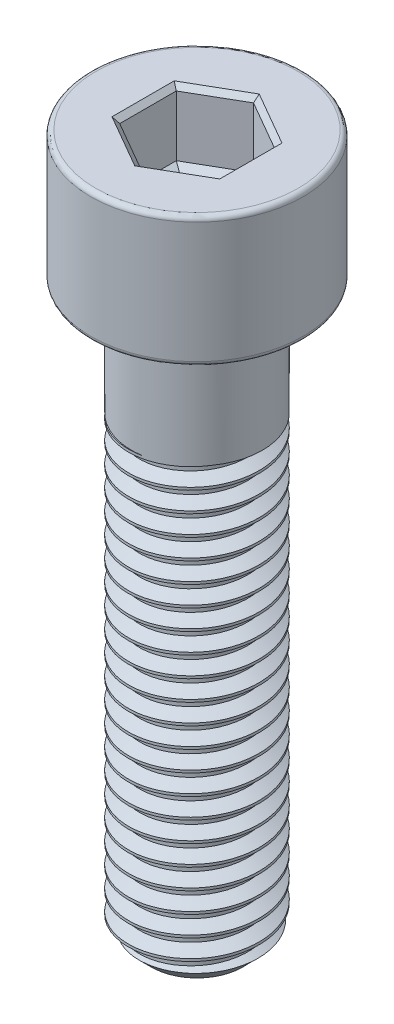
SolidWorks part; units mm, degrees
material "AISI Type A2 Tool Steel"
ref_plane "Front Plane" through (0, 0, 0) normal (0, 0, 1) x (1, 0, 0)
ref_plane "Top Plane" through (0, 0, 0) normal (0, 1, 0) x (1, 0, 0)
ref_plane "Right Plane" through (0, 0, 0) normal (1, 0, 0) x (0, 0, -1)
sketch "Sketch1" plane through (0, 0, 0) normal (0, 1, 0) x (1, 0, 0)
  circle A0 centre (0, 0) radius 4
  dimension "D1" = 8
extrude "Boss-Extrude1" add sketch "Sketch1" along normal blind 28
thread "Thread1" pitch 1.25 method cut profile "Thread Profile1" start angle 0, offset 2, length 0, pitch 1.25, diameter 8
ref_plane "Plane1" through (-4, 30, 0) normal (0, 0, 1) x (-1, 0, 0)
sketch "Thread Profile1" plane through (-4, 30, 0) normal (0, 0, 1) x (-1, 0, 0)
  line L0 (0, 0) -> (0, 1.25) construction
  line L11 (0, 0) -> (0, 1.0937)
  line L12 (0, 1.0937) -> (-0.6766, 0.7031)
  line L13 (-0.6766, 0.7031) -> (-0.6766, 0.3906)
  line L15 (-0.6766, 0.3906) -> (0, 0)
  line L17 (-0.6766, 0.5469) -> (0, 0.5469) construction
  point P2 (0, 0)
  dimension "Pitch" = 1.25
  dimension "Profile_Angle" = 60
  dimension "Profile_Land" = 0.3125
  dimension "Profile_Height" = 0.6766
sketch "Sketch2" plane through (0, 28, 0) normal (0, 1, 0) x (1, 0, 0)
  circle A0 centre (0, 0) radius 4
  dimension "D1" = 8
extrude "Boss-Extrude2" add sketch "Sketch2" along normal blind 7
sketch "Sketch5" plane through (0, 35, 0) normal (0, 1, 0) x (1, 0, 0)
  circle A0 centre (0, 0) radius 6.5
  dimension "D1" = 13
extrude "Boss-Extrude3" add sketch "Sketch5" along normal blind 8
sketch "Sketch6" plane through (0, 0, 0) normal (0, 0, 1) x (1, 0, 0)
  line L0 (0, 0) -> (0, 0.7245) construction
  line L1 (0, 0) -> (4.01, 0) construction
  line L2 (4.01, 0) -> (4.01, 1.2)
  line L3 (4.01, 1.2) -> (2.81, 0)
  line L4 (2.81, 0) -> (4.01, 0)
  dimension "D1" = 1.2
  dimension "D2" = 45
  dimension "D3" = 4.01
revolve "Cut-Revolve1" cut sketch "Sketch6" angle 360 about L0
fillet "Fillet1" radius 0.3 2 edges at (0, 35, 6.5) (0, 43, 6.5)
sketch "Sketch7" plane through (0, 43, 0) normal (0, 1, 0) x (1, 0, 0)
  line L1 (0, 3.4641) -> (-3, 1.7321)
  line L2 (-3, 1.7321) -> (-3, -1.7321)
  line L3 (-3, -1.7321) -> (0, -3.4641)
  line L4 (0, -3.4641) -> (3, -1.7321)
  line L5 (3, -1.7321) -> (3, 1.7321)
  line L6 (3, 1.7321) -> (0, 3.4641)
  circle A0 centre (0, 0) radius 3 construction
  dimension "D1" = 6
extrude "Cut-Extrude1" cut sketch "Sketch7" against normal blind 4
chamfer "Chamfer1" distance 0.3 angle 45 6 edges at (-3, 43, 0) (-1.5, 43, 2.5981) (1.5, 43, 2.5981) (3, 43, 0) (1.5, 43, -2.5981) (-1.5, 43, -2.5981)
sketch "Sketch8" plane through (0, 39, 0) normal (0, 1, 0) x (1, 0, 0)
  line L1 (0, 3.4641) -> (-3, 1.7321)
  line L2 (-3, 1.7321) -> (-3, -1.7321)
  line L3 (-3, -1.7321) -> (0, -3.4641)
  line L4 (0, -3.4641) -> (3, -1.7321)
  line L5 (3, -1.7321) -> (3, 1.7321)
  line L6 (3, 1.7321) -> (0, 3.4641)
  circle A0 centre (0, 0) radius 3 construction
extrude "Cut-Extrude2" cut sketch "Sketch8" against normal blind 0.4 draft 60
